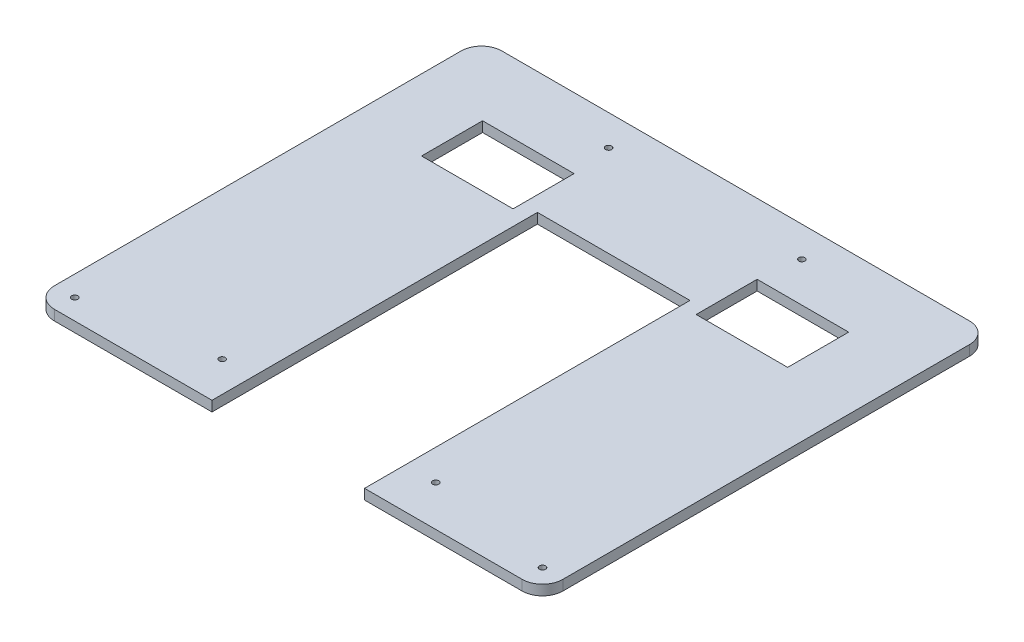
SolidWorks part; units mm, degrees
ref_plane "前视基准面" through (0, 0, 0) normal (0, 0, 1) x (1, 0, 0)
ref_plane "上视基准面" through (0, 0, 0) normal (0, 1, 0) x (1, 0, 0)
ref_plane "右视基准面" through (0, 0, 0) normal (1, 0, 0) x (0, 0, -1)
sketch "草图1" plane through (0, 0, 0) normal (0, 1, 0) x (1, 0, 0)
  line L1 (10, 0) -> (240, 0)
  line L2 (0, -10) -> (0, -210)
  line L3 (10, -220) -> (240, -220)
  line L4 (250, -10) -> (250, -210)
  arc A0 (0, -210) -> (10, -220) centre (10, -210) ccw
  arc A1 (240, -220) -> (250, -210) centre (240, -210) ccw
  arc A2 (240, 0) -> (250, -10) centre (240, -10) cw
  arc A3 (10, 0) -> (0, -10) centre (10, -10) ccw
  point P9 (250, -220)
  point P12 (250, 0)
  point P15 (0, 0)
  dimension "D3" = 10
  dimension "D1" = 250
  dimension "D2" = 220
extrude "凸台-拉伸1" add sketch "草图1" along normal blind 5
sketch "草图2" plane through (0, 0, 0) normal (0, -1, 0) x (1, 0, 0)
  line L0 (239.1778, 11.85) -> (239.1778, 76.15) construction
  line L1 (239.1778, 11.85) -> (239.1778, 76.15)
  line L2 (250, 210) -> (250, 10) construction
  line L3 (239.1778, 76.15) -> (250, 76.15)
  line L4 (239.1778, 76.15) -> (239.1778, 0)
  line L5 (239.1778, 0) -> (250, 0)
  line L6 (250, 76.15) -> (250, 0)
  line L7 (125, 220) -> (125, 0) construction
  line L8 (10, 220) -> (240, 220) construction
  line L9 (240, 0) -> (10, 0) construction
  line L10 (0, 76.15) -> (0, 0)
  line L11 (10.8222, 0) -> (0, 0)
  line L12 (10.8222, 76.15) -> (10.8222, 0)
  line L13 (10.8222, 76.15) -> (0, 76.15)
sketch "草图4" plane through (0, 0, 0) normal (0, -1, 0) x (1, 0, 0)
  line L1 (125, 0) -> (125, 220) construction
  line L2 (240, 0) -> (10, 0) construction
  line L3 (10, 220) -> (240, 220) construction
  line L8 (170, 64.475) -> (170, 34.475)
  line L16 (215, 34.475) -> (170, 34.475)
  line L17 (215, 64.475) -> (215, 34.475)
  line L18 (215, 64.475) -> (170, 64.475)
  line L19 (209.9, 64.475) -> (215, 64.475)
  line L20 (215, 64.475) -> (215, 46.825)
  line L21 (204.1, 64.475) -> (199, 64.475)
  line L22 (209.9, 64.475) -> (215, 64.475)
  line L23 (204.1, 64.475) -> (199, 64.475)
  line L24 (40.1, 64.475) -> (45.9, 64.475)
  line L25 (35, 64.475) -> (35, 46.825)
  line L26 (45.9, 64.475) -> (51, 64.475)
  line L27 (215, 64.475) -> (215, 46.825)
  line L28 (209.9, 64.475) -> (204.1, 64.475)
  line L29 (0, 10) -> (0, 210) construction
  line L30 (40.1, 64.475) -> (35, 64.475)
  line L31 (45.9, 64.475) -> (51, 64.475)
  line L33 (35, 64.475) -> (35, 46.825)
  line L35 (40.1, 64.475) -> (35, 64.475)
  line L38 (35, 64.475) -> (80, 64.475)
  line L39 (35, 64.475) -> (35, 34.475)
  line L120 (35, 34.475) -> (80, 34.475)
  line L121 (80, 64.475) -> (80, 34.475)
  dimension "D3" = 45
  dimension "D4" = 30
  dimension "D1" = 35
extrude "切除-拉伸3" cut sketch "草图4" against normal blind 5 contours L24 L30 L25 L26 | L18 L8 L16 L17 region at (57.5, 0, 49.475)
sketch "草图5" plane through (0, 0, 0) normal (0, -1, 0) x (1, 0, 0)
  line L0 (125, 220) -> (125, 0) construction
  line L1 (10, 220) -> (240, 220) construction
  line L2 (240, 0) -> (10, 0) construction
  line L3 (87.5, 220) -> (162.5, 220) construction
  line L4 (87.5, 220) -> (87.5, 60)
  line L5 (162.5, 220) -> (87.5, 220)
  line L6 (162.5, 220) -> (162.5, 60)
  line L7 (162.5, 60) -> (87.5, 60)
  point P11 (125, 60)
  dimension "D1" = 37.5
  dimension "D2" = 160
extrude "切除-拉伸4" cut sketch "草图5" against normal blind 5
sketch "草图6" plane through (0, 0, 0) normal (0, -1, 0) x (1, 0, 0)
  line L0 (72.5, 220) -> (72.5, 200) construction
  line L1 (10, 220) -> (87.5, 220) construction
  line L2 (72.5, 200) -> (87.5, 200) construction
  line L7 (87.5, 220) -> (87.5, 60) construction
  line L8 (125, 60) -> (125, 181.8158) construction
  line L9 (87.5, 60) -> (162.5, 60) construction
  line L10 (87.5, 60) -> (87.5, 0) construction
  line L11 (240, 0) -> (10, 0) construction
  line L12 (87.5, 20) -> (92.5, 20) construction
  line L13 (92.5, 20) -> (92.5, 0) construction
  line L14 (92.5, 20) -> (107.5, 20) construction
  circle A0 centre (72.5, 200) radius 1.5
  circle A3 centre (177.5, 200) radius 1.5
  dimension "D3" = 3
  dimension "D1" = 20
  dimension "D2" = 15
  dimension "D4" = 5
  dimension "D5" = 20
  dimension "D6" = 15
extrude "切除-拉伸5" cut sketch "草图6" against normal up to next contours A0 | A3
sketch "草图7" plane through (0, 0, 0) normal (0, -1, 0) x (1, 0, 0)
  line L0 (17, 15) -> (17, 73) construction
  line L1 (25, 29) -> (25, 59) construction
  line L2 (17, 44) -> (25, 44) construction
  line L3 (240, 0) -> (10, 0) construction
  line L5 (125, 60) -> (125, 0) construction
  line L6 (87.5, 60) -> (162.5, 60) construction
  line L8 (233, 44) -> (225, 44) construction
  line L9 (225, 29) -> (225, 59) construction
  line L10 (233, 15) -> (233, 73) construction
  line L11 (0, 10) -> (0, 210) construction
  circle A0 centre (17, 15) radius 1.6
  circle A1 centre (25, 29) radius 1.6
  circle A2 centre (25, 59) radius 1.6
  circle A3 centre (17, 73) radius 1.6
  circle A4 centre (233, 73) radius 1.6
  circle A5 centre (225, 59) radius 1.6
  circle A6 centre (225, 29) radius 1.6
  circle A7 centre (233, 15) radius 1.6
  dimension "D1" = 8
  dimension "D2" = 58
  dimension "D3" = 30
  dimension "D4" = 58
  dimension "D5" = 17
  dimension "D6" = 15
sketch "草图8" plane through (0, 0, 0) normal (0, -1, 0) x (1, 0, 0)
  line L0 (250, 170) -> (235, 170) construction
  line L1 (250, 210) -> (250, 10) construction
  line L2 (235, 170) -> (235, 220) construction
  line L3 (162.5, 220) -> (240, 220) construction
  line L4 (235, 170) -> (235, 100) construction
  line L5 (235, 100) -> (250, 100) construction
  line L6 (125, 60) -> (125, 122.441) construction
  line L7 (87.5, 60) -> (162.5, 60) construction
  line L8 (15, 170) -> (15, 100) construction
  circle A0 centre (235, 170) radius 1.5
  circle A1 centre (235, 100) radius 1.5
  circle A2 centre (15, 100) radius 1.5
  circle A3 centre (15, 170) radius 1.5
  dimension "D4" = 3
  dimension "D5" = 3
  dimension "D1" = 15
  dimension "D2" = 50
  dimension "D3" = 70
sketch "草图9" plane through (0, 0, 0) normal (0, -1, 0) x (1, 0, 0)
  line L0 (87.5, 60) -> (87.5, 0) construction
  line L1 (240, 0) -> (10, 0) construction
  line L2 (87.5, 0) -> (87.5, 15) construction
  line L3 (87.5, 15) -> (77.5, 15) construction
  line L4 (10, 220) -> (10, 210) construction
  line L5 (125, 60) -> (125, 0) construction
  line L6 (87.5, 60) -> (162.5, 60) construction
  circle A0 centre (77.5, 15) radius 1.5
  circle A1 centre (10, 210) radius 1.5
  circle A2 centre (240, 210) radius 1.5
  circle A3 centre (172.5, 15) radius 1.5
  dimension "D3" = 3
  dimension "D4" = 3
  dimension "D1" = 15
  dimension "D2" = 10
extrude "切除-拉伸9" cut sketch "草图9" against normal up to next
sketch "草图10" plane through (0, 0, 0) normal (0, -1, 0) x (1, 0, 0)
  line L0 (125, 60) -> (125, 0) construction
  line L1 (0, 0) -> (8, 0)
  line L2 (0, 0) -> (0, 85)
  line L3 (0, 85) -> (8, 85)
  line L4 (8, 0) -> (8, 85)
  line L5 (87.5, 60) -> (162.5, 60) construction
  line L6 (240, 0) -> (10, 0) construction
  line L7 (242, 0) -> (242, 85)
  line L8 (250, 85) -> (242, 85)
  line L9 (250, 0) -> (250, 85)
  line L10 (250, 0) -> (242, 0)
  dimension "D1" = 8
  dimension "D2" = 85
